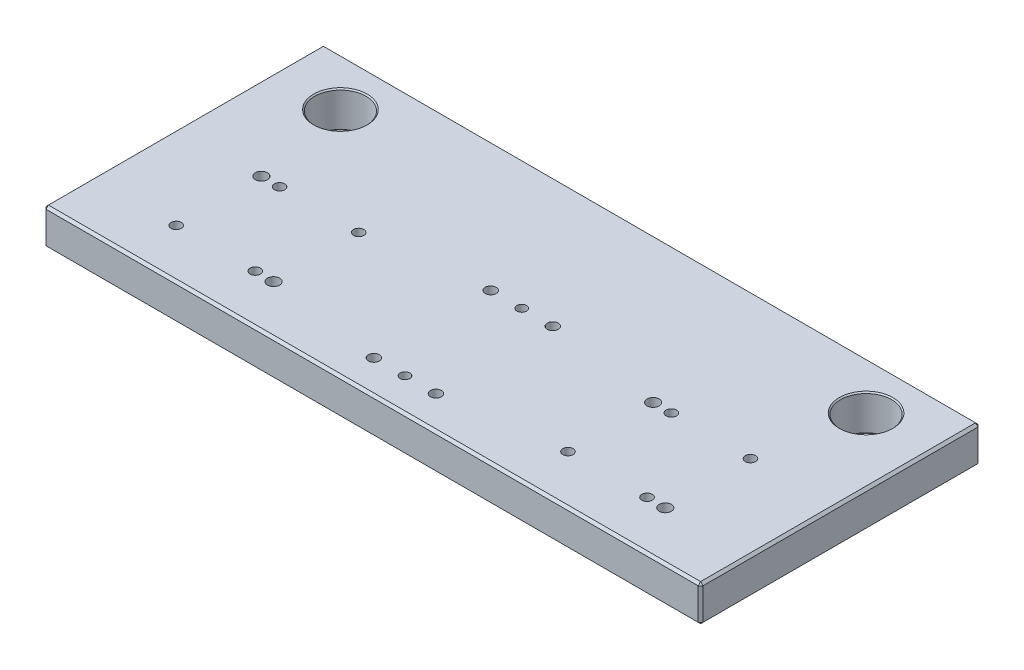
SolidWorks part; units mm, degrees
material "Plain Carbon Steel"
ref_plane "Front Plane" through (0, 0, 0) normal (0, 0, 1) x (1, 0, 0)
ref_plane "Top Plane" through (0, 0, 0) normal (0, 1, 0) x (1, 0, 0)
ref_plane "Right Plane" through (0, 0, 0) normal (1, 0, 0) x (0, 0, -1)
ref_axis "Axis1" through (0, -70, 0) along (0, 1, 0)
sketch "Sketch2" plane through (0, 0, 0) normal (0, 1, 0) x (1, 0, 0)
  line L1 (-270, -75) -> (270, -75)
  line L2 (-270, -75) -> (-270, 75)
  line L3 (-270, 75) -> (270, 75)
  line L4 (270, -75) -> (270, 75)
  line L5 (-270, -75) -> (270, 75) construction
  line L6 (-270, 75) -> (270, -75) construction
  point P0 (0, 0)
  dimension "D1" = 540
  dimension "D2" = 150
extrude "Boss-Extrude1" add sketch "Sketch2" against normal blind 30
sketch "Sketch5" plane through (0, 0, 0) normal (0, 1, 0) x (1, 0, 0)
  line L4 (270, -75) -> (270, 75)
  line L5 (270, 75) -> (-270, 75)
  line L6 (-270, 75) -> (-270, -75)
  line L7 (-270, -75) -> (270, -75)
  line L8 (270, -75) -> (270, 75) construction
  line L9 (270, 75) -> (-270, 75) construction
  line L10 (-270, 75) -> (-270, -75) construction
  line L11 (-270, -75) -> (270, -75) construction
  dimension "D1" = 0
sketch "Sketch3" plane through (0, 0, -75) normal (0, 0, -1) x (-1, 0, 0)
  line L4 (270, 0) -> (-270, 0)
  line L5 (-270, 0) -> (-270, -30)
  line L6 (-270, -30) -> (270, -30)
  line L7 (270, -30) -> (270, 0)
  line L8 (270, 0) -> (-270, 0)
  line L9 (-270, 0) -> (-270, -30)
  line L10 (-270, -30) -> (270, -30)
  line L11 (270, -30) -> (270, 0)
  dimension "D1" = 0
extrude "Boss-Extrude2" add sketch "Sketch3" along normal blind 80
sketch "Sketch6" plane through (0, 0, 0) normal (0, 1, 0) x (1, 0, 0)
  line L2 (-270, 155) -> (270, 155) construction
  circle A0 centre (-216, 115) radius 21
  dimension "D1" = 42
  dimension "D2" = 40
  dimension "D3" = 216
extrude "Cut-Extrude1" cut sketch "Sketch6" against normal through all
mirror "Mirror1" about plane through (0, 0, 0) normal (1, 0, 0) of "Cut-Extrude1"
chamfer "Chamfer1" distance 2 angle 45 12 edges at (270, -30, -40) (270, 0, -40) (0, -30, -155) (270, -15, -155) (0, 0, -155) (-270, -30, -40) (-270, -15, -155) (-270, 0, -40) (270, -15, 75) (0, -30, 75) (-270, -15, 75) (0, 0, 75)
chamfer "Chamfer2" distance 1 angle 45 4 edges at (-216, -30, -94) (216, -30, -94) (216, 0, -94) (-216, 0, -94)
hole_wizard "M10 Tapped Hole1" positions "Sketch12" profile "Sketch8" tap size "M10" standard "ISO" end condition through all
sketch "Sketch12" plane through (0, 0, 0) normal (0, 1, 0) x (1, 0, 0)
  point P7 (-121, 35)
  point P10 (-186, 35)
  point P21 (-136, -35)
  point P24 (-201, -35)
cosmetic thread "Hole Thread1"
cosmetic thread "Hole Thread2"
cosmetic thread "Hole Thread3"
cosmetic thread "Hole Thread4"
sketch "Sketch8" plane through (-121, 0, -35) normal (1, 0, 0) x (0, 0, 1)
  line L0 (0, 0) -> (0, 30)
  line L1 (0, 30) -> (4.25, 30)
  line L2 (4.25, 30) -> (4.25, 0)
  line L5 (4.25, 0) -> (0, 0)
  line L11 (0, -6.35) -> (0, 107.95) construction
  dimension "Thru Tap Drill Dia." = 8.5
  dimension "Thru Tap Drill Depth" = 30
hole_wizard "Ø10.0mm Dowel Hole1" positions "Sketch15" profile "Sketch14" hole size "Ø10.0" standard "ISO" end condition through all
sketch "Sketch15" plane through (0, 0, 0) normal (0, 1, 0) x (1, 0, 0)
  point P0 (-121, -35)
  point P3 (-201, 35)
sketch "Sketch14" plane through (-121, 0, 35) normal (1, 0, 0) x (0, 0, 1)
  line L0 (0, 0) -> (0, 30)
  line L1 (0, 30) -> (5, 30)
  line L2 (5, 30) -> (5, 0)
  line L5 (5, 0) -> (0, 0)
  line L11 (0, -6.35) -> (0, 107.95) construction
  dimension "Thru Hole Dia." = 10
  dimension "Thru Hole Depth" = 30
pattern_circular "CirPattern1" count 2 every 180 about axis through (0, -70, 0) along (0, 1, 0) of "M10 Tapped Hole1", "Ø10.0mm Dowel Hole1"
cosmetic thread "Hole Thread10"
cosmetic thread "Hole Thread11"
cosmetic thread "Hole Thread12"
cosmetic thread "Hole Thread13"
hole_wizard "CBORE for M8 Hex Socket Head Cap Screw1" positions "Sketch20" profile "Sketch17" counterbore size "M8" standard "ISO" end condition through all
sketch "Sketch20" plane through (0, -30, 0) normal (0, -1, 0) x (-1, 0, 0)
  point P0 (25.5, 48)
  point P3 (-25.5, 48)
  point P6 (-25.5, -48)
  point P9 (25.5, -48)
sketch "Sketch17" plane through (-25.5, -30, -48) normal (1, 0, 0) x (0, 0, -1)
  line L0 (0, 0) -> (0, 30)
  line L1 (0, 30) -> (4.5, 30)
  line L3 (4.5, 30) -> (4.5, 8.6)
  line L4 (4.5, 8.6) -> (7.5, 8.6)
  line L5 (7.5, 8.6) -> (7.5, 0)
  line L7 (7.5, 0) -> (0, 0)
  line L11 (0, -6.35) -> (0, 107.95) construction
  dimension "Thru Hole Dia." = 9
  dimension "Thru Hole Depth" = 30
  dimension "C'Bore Dia." = 15
  dimension "C'Bore Depth" = 8.6
hole_wizard "Ø8.0mm Dowel Hole1" positions "Sketch23" profile "Sketch22" hole size "Ø8.0" standard "ISO" end condition through all
sketch "Sketch23" plane through (0, 0, 0) normal (0, 1, 0) x (1, 0, 0)
  point P0 (0, -48)
  point P3 (0, 48)
sketch "Sketch22" plane through (0, 0, 48) normal (1, 0, 0) x (0, 0, 1)
  line L0 (0, 0) -> (0, 30)
  line L1 (0, 30) -> (4, 30)
  line L2 (4, 30) -> (4, 0)
  line L5 (4, 0) -> (0, 0)
  line L11 (0, -6.35) -> (0, 107.95) construction
  dimension "Thru Hole Dia." = 8
  dimension "Thru Hole Depth" = 30
